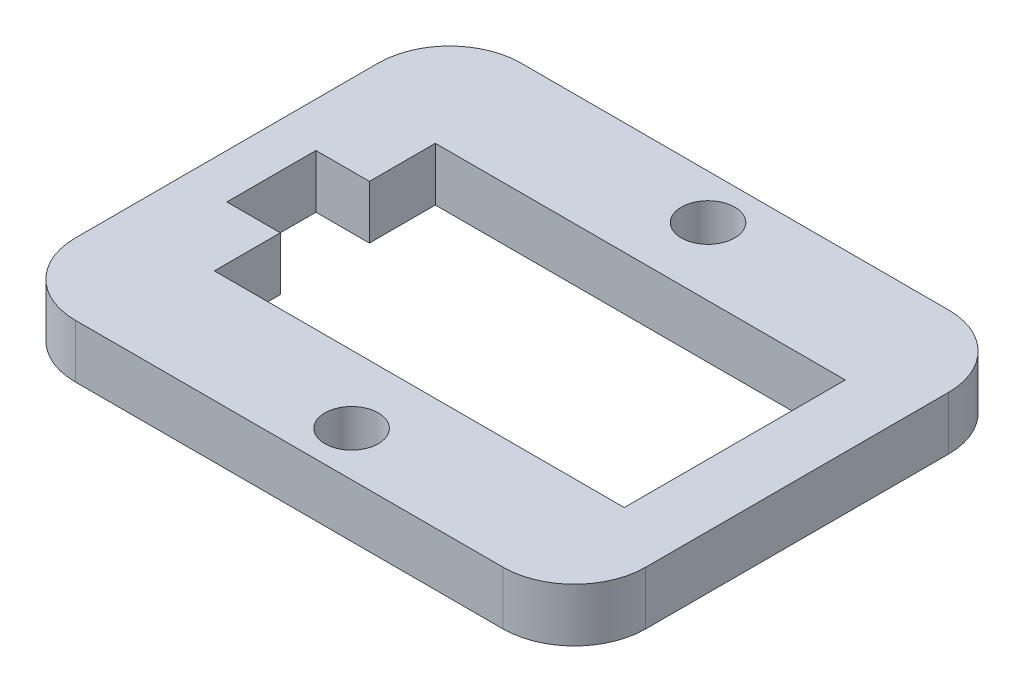
SolidWorks part; units mm, degrees
note: '?' marks a value the reader was unsure of.
material "Acrílico (médio-alto impacto)"
ref_plane "Plano frontal" through (0, 0, 0) normal (0, 0, 1) x (1, 0, 0)
ref_plane "Plano superior" through (0, 0, 0) normal (0, 1, 0) x (1, 0, 0)
ref_plane "Plano direito" through (0, 0, 0) normal (1, 0, 0) x (0, 0, -1)
sketch "Esboço1" plane through (0, 0, 0) normal (0, 1, 0) x (1, 0, 0)
  line L1 (-16, -12.5) -> (16, -12.5)
  line L2 (-16, -12.5) -> (-16, 12.5)
  line L3 (-16, 12.5) -> (16, 12.5)
  line L4 (16, -12.5) -> (16, 12.5)
  line L5 (0, 12.5) -> (0, -12.5) construction
  line L6 (-16, 0) -> (16, 0) construction
  point P0 (0, 0)
  dimension "D1" = 25
  dimension "D2" = 32
extrude "Ressalto-extrusão1" add sketch "Esboço1" along normal blind 3
sketch "Perfil Corte" plane through (-56.2297, 3, 23.2463) normal (0, 1, 0) x (1, 0, 0)
  line L0 (57.2297, 13.2463) -> (57.2297, 33.2463) construction
  line L1 (45.7297, 17.0463) -> (68.7297, 17.0463)
  line L2 (45.7297, 17.0463) -> (45.7297, 29.4463)
  line L3 (45.7297, 29.4463) -> (68.7297, 29.4463)
  line L4 (68.7297, 17.0463) -> (68.7297, 29.4463)
  line L5 (57.2297, 29.4463) -> (57.2297, 17.0463) construction
  line L6 (45.7297, 23.2463) -> (68.7297, 23.2463) construction
  line L7 (68.7297, 23.2463) -> (72.2297, 23.2463) construction
  line L8 (72.2297, 10.7463) -> (72.2297, 35.7463) construction
  line L9 (72.2297, 35.7463) -> (40.2297, 35.7463) construction
  point P0 (57.2297, 23.2463)
  point P7 (57.2297, 23.2463)
  dimension "D1" = 23
  dimension "entre furos" = 20
  dimension "D2" = 12.4
  dimension "Afastamento Lateral" = 15
  dimension "Posicionamento Altura" = 12.5
sketch "Esboço6" plane through (-54.7734, 3, 25) normal (0, 1, 0) x (1, 0, 0)
  line L1 (41.2734, 27.5) -> (44.2734, 27.5)
  line L2 (41.2734, 27.5) -> (41.2734, 22.5)
  line L3 (41.2734, 22.5) -> (44.2734, 22.5)
  line L4 (44.2734, 27.5) -> (44.2734, 22.5)
  line L5 (42.7734, 22.5) -> (42.7734, 27.5) construction
  line L6 (41.2734, 25) -> (44.2734, 25) construction
  point P0 (42.7734, 25)
  dimension "D1" = 3
  dimension "D2" = 5
extrude "Corte Principal" cut sketch "Perfil Corte" against normal through all
hole_wizard "Furo de diâmetro Ø3.0 (3)1" positions "Esboço4" profile "Esboço5" hole size "Ø3.0" standard "ISO" end condition through all
sketch "Esboço4" plane through (-54.7734, 3, 25) normal (0, 1, 0) x (1, 0, 0)
  point P0 (55.7734, 35)
  point P3 (55.7734, 15)
sketch "Esboço5" plane through (1, 3, -10) normal (1, 0, 0) x (0, 0, 1)
  line L0 (0, 0) -> (0, 3)
  line L1 (0, 3) -> (1.5, 3)
  line L2 (1.5, 3) -> (1.5, 0)
  line L5 (1.5, 0) -> (0, 0)
  line L11 (0, -6.35) -> (0, 107.95) construction
  dimension "Thru Hole Dia." = 3
  dimension "Thru Hole Depth" = 3
extrude "Corte-extrusão2" cut sketch "Esboço6" against normal through all
other "Furos Motor<1>"
fillet "Filete1" radius 4 4 edges at (-16, 1.5, 12.5) (-16, 1.5, -12.5) (16, 1.5, -12.5) (16, 1.5, 12.5)
sketch "Esboço7" plane through (0, 0, 0) normal (0, 0, 1) x (1, 0, 0)
  line L0 (-12, 3) -> (-12, 0)
  line L1 (-10.5, 3) -> (-13.5, 3) construction
  line L2 (-10.5, 0) -> (-13.5, 0) construction
other "PontoR1"
other "PontoR2"
ref_axis "Eixo1" through (-12, 3, 0) along (0, -1, 0)?
